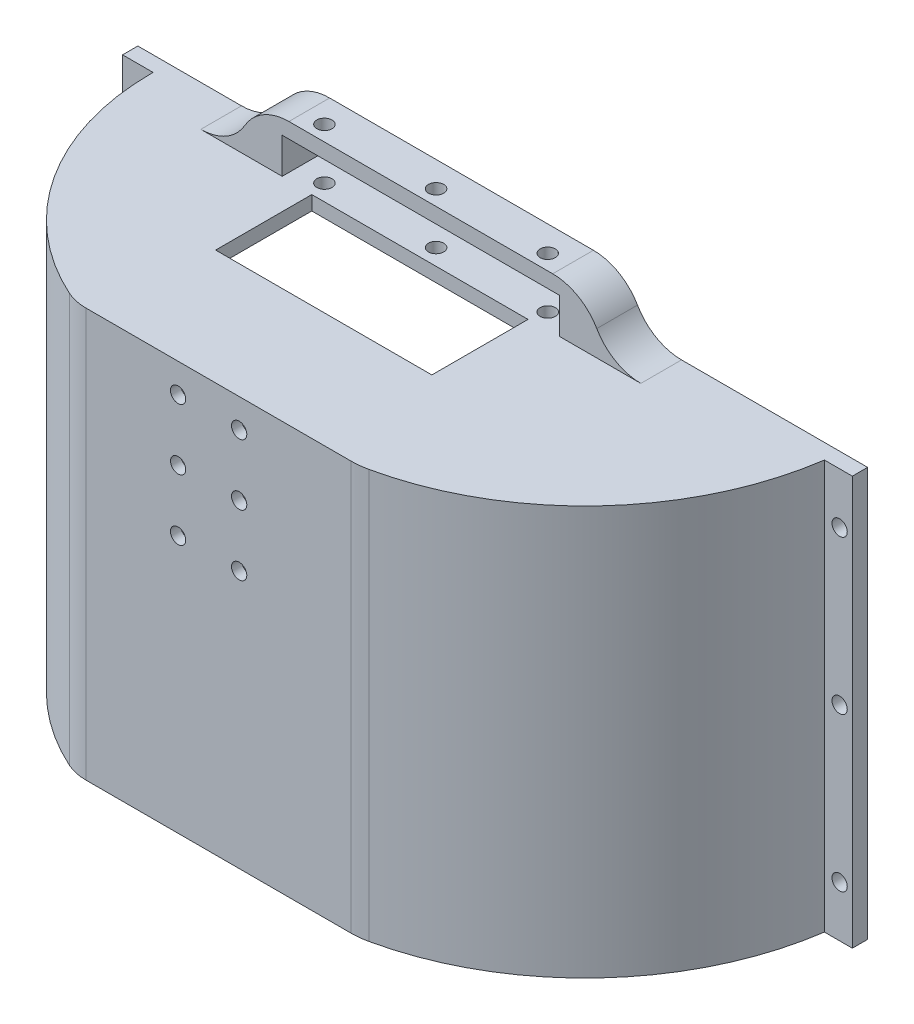
SolidWorks part; units mm, degrees
ref_plane "前视基准面" through (0, 0, 0) normal (0, 0, 1) x (1, 0, 0)
ref_plane "上视基准面" through (0, 0, 0) normal (0, 1, 0) x (1, 0, 0)
ref_plane "右视基准面" through (0, 0, 0) normal (1, 0, 0) x (0, 0, -1)
other "Configuration Table"
sketch "草图1" plane through (0, 0, 0) normal (0, 0, 1) x (1, 0, 0)
  line L0 (-77.3109, 43.4948) -> (-77.3109, -31.0552) construction
  line L1 (-77.3109, -31.0552) -> (50.1101, -31.0552) construction
  line L2 (50.1101, 43.4948) -> (-98.3152, 43.4948) construction
  line L3 (50.1101, -31.0552) -> (50.1101, 43.4948) construction
  line L4 (-85.3152, -34.0552) -> (58.1101, -34.0552)
  line L5 (58.1101, -34.0552) -> (58.1101, 46.2948)
  line L6 (58.1101, 46.2948) -> (-85.3152, 46.2948)
  line L7 (-85.3152, 46.2948) -> (-85.3152, -34.0552)
  line L8 (-85.3152, -34.0552) -> (58.1101, -34.0552)
  line L9 (58.1101, -34.0552) -> (58.1101, 46.2948)
  line L10 (58.1101, 46.2948) -> (-85.3152, 46.2948)
  line L11 (-85.3152, 46.2948) -> (-85.3152, -34.0552)
  line L12 (-77.3109, 43.4948) -> (-77.3109, -31.0552)
  line L13 (-77.3109, -31.0552) -> (50.1101, -31.0552)
  line L14 (50.1101, 43.4948) -> (-77.3109, 43.4948)
  line L15 (50.1101, -31.0552) -> (50.1101, 43.4948)
  circle A0 centre (55.6101, -24.0552) radius 1.5 construction
  circle A1 centre (55.6101, 6.1198) radius 1.5 construction
  circle A2 centre (55.6101, 36.2948) radius 1.5 construction
  circle A3 centre (-82.8109, -24.0552) radius 1.5 construction
  circle A4 centre (-82.8109, 6.1198) radius 1.5 construction
  circle A5 centre (-82.8109, 36.2948) radius 1.5 construction
  circle A6 centre (55.6101, -24.0552) radius 1.5
  circle A7 centre (55.6101, 6.1198) radius 1.5
  circle A8 centre (55.6101, 36.2948) radius 1.5
  circle A9 centre (-82.8109, -24.0552) radius 1.5
  circle A10 centre (-82.8109, 6.1198) radius 1.5
  circle A11 centre (-82.8109, 36.2948) radius 1.5
  dimension "D1" = 0
extrude "凸台-拉伸1" add sketch "草图1" along normal blind 3
sketch "草图2" plane through (0, 46.2948, 0) normal (0, 1, 0) x (1, 0, 0)
  line L0 (58.1101, -3) -> (-85.3152, -3) construction
  line L1 (52.1101, -3) -> (-79.3152, -3)
  line L2 (52.1101, -3) -> (52.1101, -8)
  line L3 (52.1101, -8) -> (-79.3152, -8)
  line L4 (-79.3152, -3) -> (-79.3152, -8)
  line L5 (58.1101, -3) -> (58.1101, 0) construction
  line L6 (-85.3152, -3) -> (-85.3152, 0) construction
  line L7 (-21.7025, -953.5) -> (-21.7025, 49046.5) construction
  line L8 (-52.0899, 46.5) -> (8.6848, 46.5) construction
  circle A0 centre (-21.7025, -5) radius 1.5
  point P15 (-21.7025, 46.5)
  dimension "D5" = 3
  dimension "D1" = 6
  dimension "D2" = 6
  dimension "D3" = 5
  dimension "D4" = 2
extrude "凸台-拉伸2" add sketch "草图2" against normal blind 2.8
sketch "草图3" plane through (0, 46.2948, 0) normal (0, 1, 0) x (1, 0, 0)
  line L0 (-999.7596, -5) -> (49000.2404, -5) construction
  circle A0 centre (0.2404, -5) radius 1.5
  circle A1 centre (-43.6455, -5) radius 1.5
  dimension "D1" = 3
  dimension "D2" = 3
extrude "切除-拉伸1" cut sketch "草图3" against normal blind 10
sketch "草图4" plane through (0, 46.2948, 0) normal (0, 1, 0) x (1, 0, 0)
  line L0 (-77.3109, 0) -> (50.1101, 0) construction
  line L1 (5.5404, 0) -> (11.5404, 0)
  line L2 (5.5404, 0) -> (5.5404, -8)
  line L3 (5.5404, -8) -> (11.5404, -8)
  line L4 (11.5404, 0) -> (11.5404, -8)
  line L5 (-79.3152, -8) -> (52.1101, -8) construction
  line L6 (5.2404, -16.5556) -> (5.2404, 0) construction
  line L7 (-48.9455, 0) -> (-54.9455, 0)
  line L8 (-48.9455, 0) -> (-48.9455, -8)
  line L9 (-48.9455, -8) -> (-54.9455, -8)
  line L10 (-54.9455, 0) -> (-54.9455, -8)
  line L11 (-48.6455, 0) -> (-48.6455, -16.5556) construction
  dimension "D1" = 6
  dimension "D2" = 6
  dimension "D3" = 0.3
  dimension "D4" = 0.3
extrude "凸台-拉伸3" add sketch "草图4" along normal blind 10
sketch "草图5" plane through (0, 56.2948, 0) normal (0, 1, 0) x (1, 0, 0)
  line L1 (5.5404, -8) -> (-48.9455, -8)
  line L2 (5.5404, -8) -> (5.5404, 0)
  line L3 (5.5404, 0) -> (-48.9455, 0)
  line L4 (-48.9455, -8) -> (-48.9455, 0)
extrude "凸台-拉伸4" add sketch "草图5" against normal blind 3
fillet "圆角1" radius 10 2 edges at (11.5404, 46.2948, 4) (-54.9455, 46.2948, 4)
fillet "圆角2" radius 10 2 edges at (-54.9455, 56.2948, 4) (11.5404, 56.2948, 4)
sketch "草图6" plane through (0, 56.2948, 0) normal (0, 1, 0) x (1, 0, 0)
  circle A0 centre (0.2404, -5) radius 1.5
  circle A1 centre (-21.7025, -5) radius 1.5
  circle A2 centre (-43.6455, -5) radius 1.5
  dimension "D1" = 3
  dimension "D2" = 3
  dimension "D3" = 3
extrude "切除-拉伸2" cut sketch "草图6" against normal blind 3
sketch "草图7" plane through (0, 46.2948, 0) normal (0, 1, 0) x (1, 0, 0)
  line L0 (-47.8552, -50) -> (4.4502, -50) construction
  line L1 (-47.8552, -50) -> (4.4502, -50) construction
  line L2 (52.1101, -3) -> (-79.3152, -3)
  line L3 (-45.8212, -49.7) -> (3.801, -49.7)
  line L4 (-47.8552, -49.7) -> (4.4502, -49.7) construction
  arc A0 (52.1101, -3) -> (5.1618, -49.607) centre (-2.3222, 4.8814) cw
  arc A1 (-79.3152, -3) -> (-49.9475, -48.809) centre (-29.3159, -3.2641) ccw
  arc A2 (-45.8212, -49.7) -> (-49.9475, -48.809) centre (-45.8212, -39.7) cw
  arc A3 (3.801, -49.7) -> (5.1618, -49.607) centre (3.801, -39.7) ccw
  dimension "D2" = 55
  dimension "D3" = 50
  dimension "D4" = 10
  dimension "D5" = 10
  dimension "D6" = 48.3091
  dimension "D1" = 0.3
  dimension "D7" = 33.494
extrude "凸台-拉伸5" add sketch "草图7" against normal up to surface (2.8 mm away)
sketch "草图8" plane through (0, 46.2948, 0) normal (0, 1, 0) x (1, 0, 0)
  line L0 (52.1101, -3) -> (52.1101, -8) construction
  line L1 (52.1101, -8) -> (-79.3152, -8) construction
  line L2 (-79.3152, -3) -> (-79.3152, -8) construction
  line L3 (52.1101, -3) -> (52.1101, -8)
  line L4 (52.1101, -8) -> (51.148, -8)
  line L5 (-79.3152, -3) -> (-79.3152, -8)
  line L6 (-79.0911, -8) -> (-79.3152, -8)
  line L7 (-42.9375, -8.1913) -> (-42.9375, -19.0913) construction
  line L8 (-0.4375, -19.0913) -> (-42.9375, -19.0913) construction
  line L9 (-0.4375, -19.0913) -> (-0.4375, -8.1913)
  line L10 (-0.4375, -8.1913) -> (-42.9375, -8.1913)
  line L11 (-42.9375, -19.0913) -> (-42.9375, -8.1913)
  line L12 (-42.9375, -8.1913) -> (-0.4375, -8.1913) construction
  line L14 (-42.9375, -19.0913) -> (-0.4375, -19.0913) construction
  line L15 (-42.9375, -19.0913) -> (-42.9375, -27.0913)
  line L16 (-42.9375, -27.0913) -> (-0.4375, -27.0913)
  line L17 (-0.4375, -19.0913) -> (-0.4375, -27.0913)
  arc A0 (5.1618, -49.607) -> (52.1101, -3) centre (-2.3222, 4.8814) ccw construction
  arc A1 (-79.3152, -3) -> (-49.9475, -48.809) centre (-29.3159, -3.2641) ccw construction
  arc A2 (51.148, -8) -> (52.1101, -3) centre (-2.3222, 4.8814) ccw
  arc A3 (-79.3152, -3) -> (-79.0911, -8) centre (-29.3159, -3.2641) ccw
  circle A4 centre (0.2404, -5) radius 1.5 construction
  circle A5 centre (-43.6455, -5) radius 1.5 construction
  circle A6 centre (-21.7025, -5) radius 1.5 construction
  circle A7 centre (0.2404, -5) radius 1.5
  circle A8 centre (-43.6455, -5) radius 1.5
  circle A9 centre (-21.7025, -5) radius 1.5
  line M1 (52.1101, -8) -> (52.1101, -3)
  line M16 (-79.3152, -3.5282) -> (-79.3152, -8)
  line M17 (-79.3152, -8) -> (-79.0911, -8)
  line M23 (51.148, -8) -> (52.1101, -8)
  dimension "D1" = 3
  dimension "D2" = 3
  dimension "D3" = 3
  dimension "D4" = 8
extrude "切除-拉伸3" cut sketch "草图8" against normal blind 3 contours A2 M23 M1 | A3 M16 M17 | L11 L8 L9 L10 | A7 | A9 | A8
sketch "草图9" plane through (0, 43.4948, 0) normal (0, -1, 0) x (1, 0, 0)
  line L0 (-45.8212, 49.7) -> (3.801, 49.7) construction
  line L1 (-48.3212, 49.7) -> (6.2544, 49.7)
  line L2 (52.1101, 3) -> (-79.3152, 3) construction
  line L3 (52.6153, 3) -> (50.1101, 3)
  line L5 (-45.8212, 47.7) -> (3.801, 47.7)
  line L8 (52.1101, 3) -> (-79.3152, 3) construction
  line L9 (52.6847, 2.5) -> (-79.8101, 2.5) construction
  line L10 (49.7485, 5) -> (-77.2845, 5) construction
  line L11 (-77.2845, 5) -> (-77.2845, 3)
  line L12 (49.7485, 5) -> (50.1101, 3)
  line L13 (-77.2845, 3) -> (-79.8152, 3)
  line L14 (-45.8212, 50.2) -> (3.801, 50.2) construction
  line L15 (-45.8212, 49.7) -> (3.801, 49.7) construction
  arc A0 (5.1618, 49.607) -> (3.801, 49.7) centre (3.801, 39.7) ccw construction
  arc A1 (52.1101, 3) -> (5.1618, 49.607) centre (-2.3222, -4.8814) ccw construction
  arc A2 (-48.3212, 49.7) -> (-49.8596, 49.3923) centre (-48.3212, 45.7) ccw
  arc A3 (-49.9475, 48.809) -> (-79.3152, 3) centre (-29.3159, 3.2641) ccw construction
  arc A4 (5.1618, 49.607) -> (3.801, 49.7) centre (3.801, 39.7) ccw construction
  arc A5 (52.1101, 3) -> (5.1618, 49.607) centre (-2.3222, -4.8814) ccw construction
  arc A7 (-49.9475, 48.809) -> (-79.3152, 3) centre (-29.3159, 3.2641) ccw construction
  arc A8 (-49.1222, 46.9872) -> (-77.2845, 5) centre (-29.3159, 3.2641) ccw
  arc A9 (49.7485, 5) -> (4.8896, 47.6256) centre (-2.3222, -4.8814) ccw
  arc A10 (4.8896, 47.6256) -> (3.801, 47.7) centre (3.801, 39.7) ccw
  arc A11 (-45.8212, 47.7) -> (-49.1222, 46.9872) centre (-45.8212, 39.7) ccw
  arc A12 (-50.1538, 49.2644) -> (-79.8152, 3) centre (-29.3159, 3.2641) ccw
  arc A13 (52.6153, 3) -> (9.4309, 49.3598) centre (-2.3222, -4.8814) ccw
  arc A15 (-49.8596, 49.3923) -> (-50.1538, 49.2644) centre (-45.8212, 39.7) ccw
  arc A16 (52.6847, 2.5) -> (5.2298, 50.1023) centre (-2.3222, -4.8814) ccw construction
  arc A17 (-50.1538, 49.2644) -> (-79.8101, 2.5) centre (-29.3159, 3.2641) ccw construction
  arc A18 (5.2298, 50.1023) -> (3.801, 50.2) centre (3.801, 39.7) ccw construction
  arc A19 (-45.8212, 49.7) -> (-49.9475, 48.809) centre (-45.8212, 39.7) ccw construction
  arc A20 (-45.8212, 50.2) -> (-50.1538, 49.2644) centre (-45.8212, 39.7) ccw construction
  arc A21 (9.4309, 49.3598) -> (6.2544, 49.7) centre (6.2544, 34.7) ccw
  dimension "D3" = 8
  dimension "D4" = 4
  dimension "D5" = 15
  dimension "D1" = 2
  dimension "D2" = 0.5
extrude "凸台-拉伸6" add sketch "草图9" along normal up to surface and the other way blind 2.8
sketch "草图11" plane through (0, 0, 47.7) normal (0, 0, -1) x (-1, 0, 0)
  circle A0 centre (15.7025, 40.5948) radius 1.5
  circle A1 centre (27.7025, 40.5948) radius 1.5
  circle A2 centre (15.7025, 28.5948) radius 1.5
  circle A3 centre (27.7025, 28.5948) radius 1.4903
  circle A4 centre (27.7025, 16.5948) radius 1.5
  circle A5 centre (15.7025, 16.5948) radius 1.5
  dimension "D1" = 3
  dimension "D2" = 3
  dimension "D3" = 3
  dimension "D4" = 3
  dimension "D5" = 3
extrude "切除-拉伸4" cut sketch "草图11" against normal blind 3
sketch "草图12" plane through (0, -34.0552, 0) normal (0, -1, 0) x (1, 0, 0)
  line L0 (52.1101, 3) -> (-79.3152, 3) construction
  line L1 (-45.8212, 49.7) -> (6.2544, 49.7) construction
  line L2 (-45.8212, 49.7) -> (3.801, 49.7) construction
  line L3 (52.1101, 3) -> (-79.3152, 3)
  line L4 (-45.8212, 49.7) -> (6.2544, 49.7)
  line L5 (-45.8212, 49.7) -> (3.801, 49.7)
  line L6 (52.1101, 3) -> (52.6153, 3)
  arc A0 (52.6153, 3) -> (9.4309, 49.3598) centre (-2.3222, -4.8814) ccw construction
  arc A1 (9.4309, 49.3598) -> (6.2544, 49.7) centre (6.2544, 34.7) ccw construction
  arc A2 (-45.8212, 49.7) -> (-49.9475, 48.809) centre (-45.8212, 39.7) ccw construction
  arc A3 (-49.9475, 48.809) -> (-79.3152, 3) centre (-29.3159, 3.2641) ccw construction
  arc A4 (52.6153, 3) -> (9.4309, 49.3598) centre (-2.3222, -4.8814) ccw
  arc A5 (9.4309, 49.3598) -> (6.2544, 49.7) centre (6.2544, 34.7) ccw
  arc A6 (-45.8212, 49.7) -> (-49.9475, 48.809) centre (-45.8212, 39.7) ccw
  arc A7 (-49.9475, 48.809) -> (-79.3152, 3) centre (-29.3159, 3.2641) ccw
  line M1 (-79.3152, 3.5282) -> (-79.3152, 3)
  arc M7 (52.6153, 3) -> (9.4309, 49.3598) centre (-2.3222, -4.8814) ccw
  arc M8 (9.4309, 49.3598) -> (6.2544, 49.7) centre (6.2544, 34.7) ccw
  line M9 (6.2544, 49.7) -> (-45.8212, 49.7)
  arc M10 (-45.8212, 49.7) -> (-49.9475, 48.809) centre (-45.8212, 39.7) ccw
  arc M11 (-49.9475, 48.809) -> (-79.3152, 3.5282) centre (-29.3159, 3.2641) ccw
  line M12 (50.1101, 3) -> (-77.2845, 3)
  line M13 (-77.2845, 3) -> (-77.2845, 5)
  arc M14 (-77.2845, 5) -> (-49.1222, 46.9872) centre (-29.3159, 3.2641) cw
  arc M15 (-49.1222, 46.9872) -> (-45.8212, 47.7) centre (-45.8212, 39.7) cw
  line M16 (-45.8212, 47.7) -> (3.801, 47.7)
  arc M17 (3.801, 47.7) -> (4.8896, 47.6256) centre (3.801, 39.7) cw
  arc M18 (4.8896, 47.6256) -> (49.7485, 5) centre (-2.3222, -4.8814) cw
  line M19 (49.7485, 5) -> (50.1101, 3)
extrude "凸台-拉伸7" add sketch "草图12" against normal up to surface (3 mm away) contours M12 M19 M18 M17 M16 M15 M14 M13 | L3 L6 L4 M7 M8 M9 M10 M11 M1 M13 M14 M15 M16 M17 M18 M19 up to face at (-26.3372, -31.0552, 1.8)
